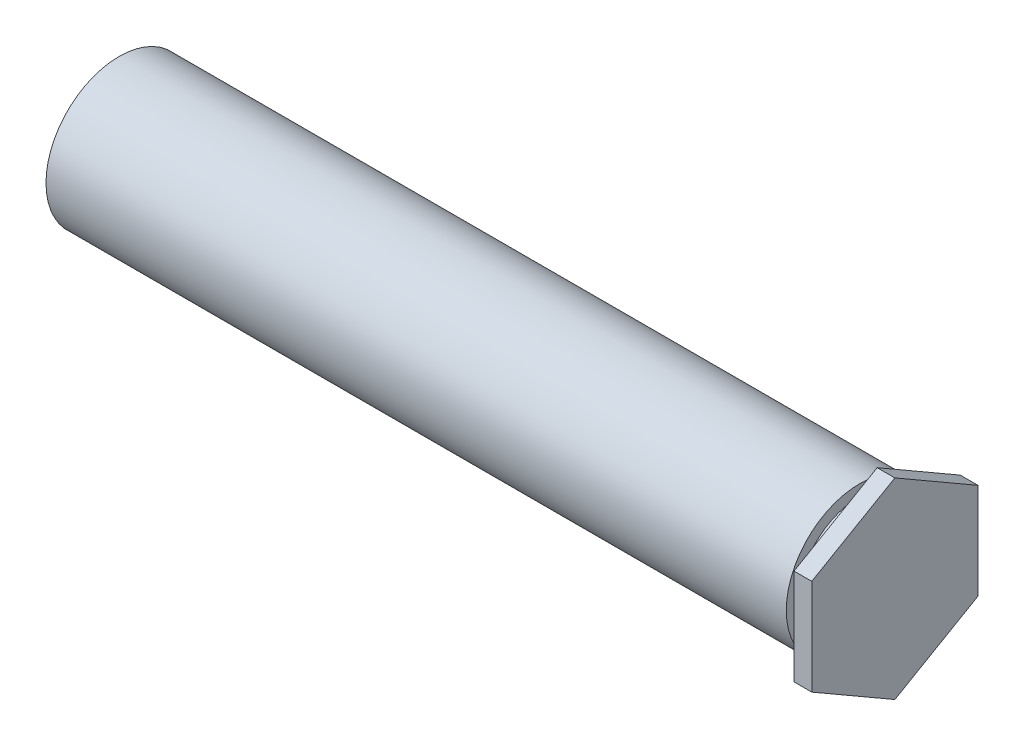
SolidWorks part; units mm, degrees
material "Alloy Steel (SS)"
ref_plane "Front Plane" through (0, 0, 0) normal (0, 0, 1) x (1, 0, 0)
ref_plane "Top Plane" through (0, 0, 0) normal (0, 1, 0) x (1, 0, 0)
ref_plane "Right Plane" through (0, 0, 0) normal (1, 0, 0) x (0, 0, -1)
sketch "Sketch1" plane through (0, 0, 0) normal (0, 0, 1) x (1, 0, 0)
  line L0 (-11.1125, 0) -> (11.1125, 0) construction
  line L1 (-11.1125, 2.0955) -> (-11.1125, -2.0955) construction
  line L2 (-1.5875, 1.4224) -> (-1.5875, -1.4224) construction
  line L3 (11.1125, 2.3813) -> (11.1125, -2.3813) construction
  line L4 (-1.5875, 1.4224) -> (-11.1125, 1.4224) construction
  line L5 (-1.5875, -1.4224) -> (-11.1125, -1.4224) construction
  point P4 (-1.5875, 0)
  point P10 (10.6045, 0)
  point P11 (10.0965, 0)
  dimension "OD" = 4.191
  dimension "Length" = 22.225
  dimension "Thread Height" = 9.525
  dimension "Thread Size" = 2.8448
  dimension "Hex" = 4.7625
  dimension "D4" = 0.508
  dimension "Panelthickness" = 1.016
ref_plane "Plane1" through (-11.1125, 0, 0) normal (1, 0, 0) x (0, 0, -1)
sketch "Sketch2" plane through (-11.1125, 0, 0) normal (1, 0, 0) x (0, 0, -1)
  circle A0 centre (0, 0) radius 2.0955
extrude "Extrude1" add sketch "Sketch2" along normal up to vertex (22.225 mm away) up to point (11.1125, 0, 0)
sketch "Sketch3" plane through (11.1125, 0, 0) normal (1, 0, 0) x (0, 0, -1)
  line L1 (0, 2.7496) -> (-2.3813, 1.3748)
  line L2 (-2.3813, 1.3748) -> (-2.3813, -1.3748)
  line L3 (-2.3813, -1.3748) -> (0, -2.7496)
  line L4 (0, -2.7496) -> (2.3813, -1.3748)
  line L5 (2.3813, -1.3748) -> (2.3813, 1.3748)
  line L6 (2.3813, 1.3748) -> (0, 2.7496)
  circle A0 centre (0, 0) radius 2.3813 construction
extrude "Extrude2" add sketch "Sketch3" against normal up to vertex (0.508 mm away) up to point (10.6045, 0, 0)
sketch "Sketch4" plane through (10.6045, 0, 0) normal (-1, 0, 0) x (0, 0, 1)
  circle A0 centre (0, 0) radius 1.778
  circle A1 centre (0, 0) radius 2.0955 construction
  circle A2 centre (0, 0) radius 2.0955
  dimension "D1" = 0.3175
extrude "Extrude3" cut sketch "Sketch4" along normal up to vertex (0.508 mm away) up to point (10.0965, 0, 0)
sketch "Sketch5" plane through (-11.1125, 0, 0) normal (-1, 0, 0) x (0, 0, 1)
  line L0 (0, 0) -> (-1.0058, 1.0058) construction
  line L1 (0, 0) -> (-1.4224, 0) construction
  circle A0 centre (0, 0) radius 1.4224
  dimension "D1" = 45
extrude "Extrude4" cut sketch "Sketch5" against normal up to vertex (9.525 mm away) up to point (-1.5875, 0, 0)
sketch "Sketch6" plane through (-11.1125, 0, 0) normal (-1, 0, 0) x (0, 0, 1)
  circle A1 centre (0, 0) radius 1.4224
  circle A2 centre (0, 0) radius 1.4224
  dimension "D1" = 0
curve "Helix/Spiral1" pitch 0.635 height 9.525 turns 15 parameters "Pitch"=0.635
sketch "Sketch7" plane through (0, 0, 0) normal (0, 0, 1) x (1, 0, 0)
  line L0 (-11.6681, 1.4224) -> (-11.1125, 1.4224)
  line L1 (-11.6681, 1.4224) -> (-11.43, 1.01)
  line L2 (-11.43, 1.01) -> (-11.3506, 1.01)
  line L3 (-11.3506, 1.01) -> (-11.1125, 1.4224)
  line L4 (-11.3903, 1.01) -> (-11.3903, 1.4224) construction
  line L5 (-11.5491, 1.2162) -> (-11.2316, 1.2162) construction
  dimension "D1" = 60
  dimension "D2" = 0.0794
  dimension "D3" = 0.3175
sweep "Sweep1" add profiles "Sketch7" path "Helix/Spiral1"
sketch "Sketch8" plane through (-11.1125, 0, 0) normal (-1, 0, 0) x (0, 0, 1)
  circle A2 centre (0, 0) radius 1.4732
  circle A3 centre (0, 0) radius 1.4732
  dimension "D1" = 0.0508
extrude "Extrude6" cut sketch "Sketch8" along normal through all and the other way through all draft 45
sketch "Sketch9" plane through (-11.1125, 0, 0) normal (-1, 0, 0) x (0, 0, 1)
  line L0 (0, 0) -> (0, -2.0955) construction
  line L1 (0, 0) -> (-1.4817, -1.4817) construction
  line L2 (0, 0) -> (-2.0955, 0) construction
  circle A0 centre (0, 0) radius 2.0955 construction
  circle A1 centre (0, 0) radius 1.4732 construction
  point P6 (-0.71, -0.71)
  point P8 (-1.4817, -1.4817)
  point P9 (-1.0417, -1.0417)
  point P13 (-1.1477, 0)
  point P14 (-1.0417, 0)
  dimension "D1" = 45
  dimension "D2" = 45
equation "\"D2@Sketch7\" = \"Pitch@Helix/Spiral1\"*.125"
equation "\"D3@Sketch7\" = \"Pitch@Helix/Spiral1\"*.5"
equation "\"D3@Helix/Spiral1\" = \"Thread Height@Sketch1\""
